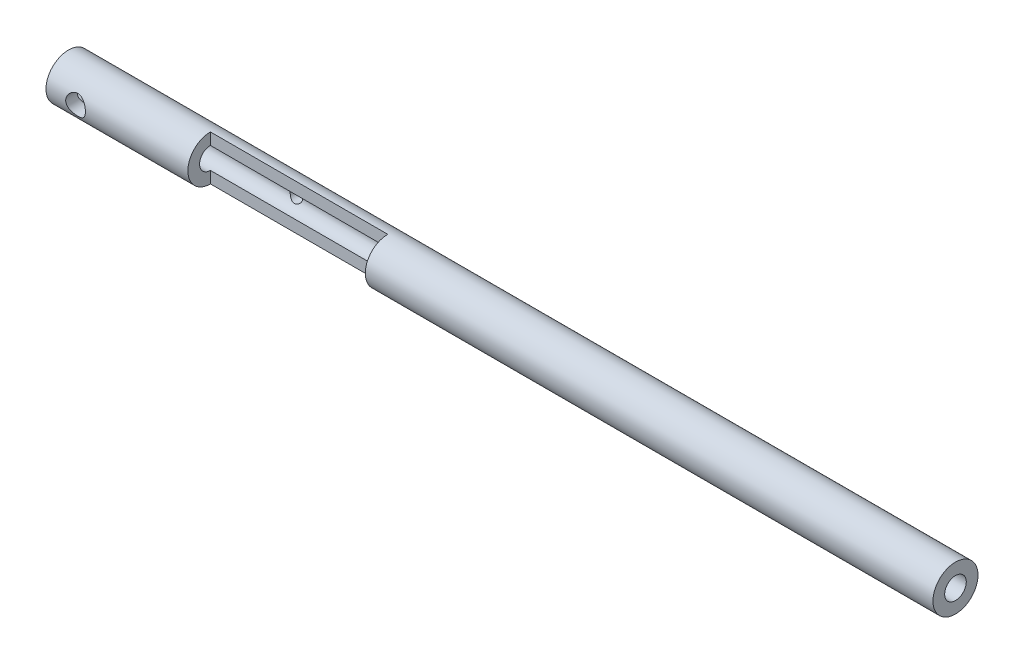
SolidWorks part; units mm, degrees
ref_plane "Front Plane" through (0, 0, 0) normal (0, 0, 1) x (1, 0, 0)
ref_plane "Top Plane" through (0, 0, 0) normal (0, 1, 0) x (1, 0, 0)
ref_plane "Right Plane" through (0, 0, 0) normal (1, 0, 0) x (0, 0, -1)
sketch "Sketch1" plane through (0, 0, 0) normal (1, 0, 0) x (0, 0, -1)
  circle A0 centre (0, 0) radius 3.175
  circle A1 centre (0, 0) radius 1.524
  dimension "D1" = 6.35
  dimension "D2" = 3.048
extrude "Boss-Extrude1" add sketch "Sketch1" along normal blind 125
sketch "Sketch2" plane through (0, 0, 0) normal (0, 0, 1) x (1, 0, 0)
  line L0 (0, 3.175) -> (0, -3.175) construction
  line L1 (0, 3.175) -> (0, -3.175) construction
  line L2 (0, 0) -> (4.1717, 0) construction
  circle A0 centre (4.1717, 0) radius 1.3894
  dimension "D1" = 2.7788
extrude "5-40 hole for set screw attaching shaft" cut sketch "Sketch2" against normal blind 10 and the other way blind 10
sketch "Sketch3" plane through (0, 0, 0) normal (0, 0, 1) x (1, 0, 0)
  line L1 (20, 5.637) -> (45, 5.637)
  line L2 (20, 5.637) -> (20, -9.1965)
  line L3 (20, -9.1965) -> (45, -9.1965)
  line L4 (45, 5.637) -> (45, -9.1965)
  line L6 (0, 3.175) -> (0, -3.175) construction
  dimension "D1" = 25
  dimension "D2" = 20
extrude "Cut-Extrude2" cut sketch "Sketch3" along normal through all
sketch "Sketch4" plane through (0, 0, 0) normal (0, 0, 1) x (1, 0, 0)
  circle A0 centre (30.5964, 0) radius 0.889
  dimension "D1" = 1.778
extrude "Cut-Extrude3" cut sketch "Sketch4" against normal blind 3
